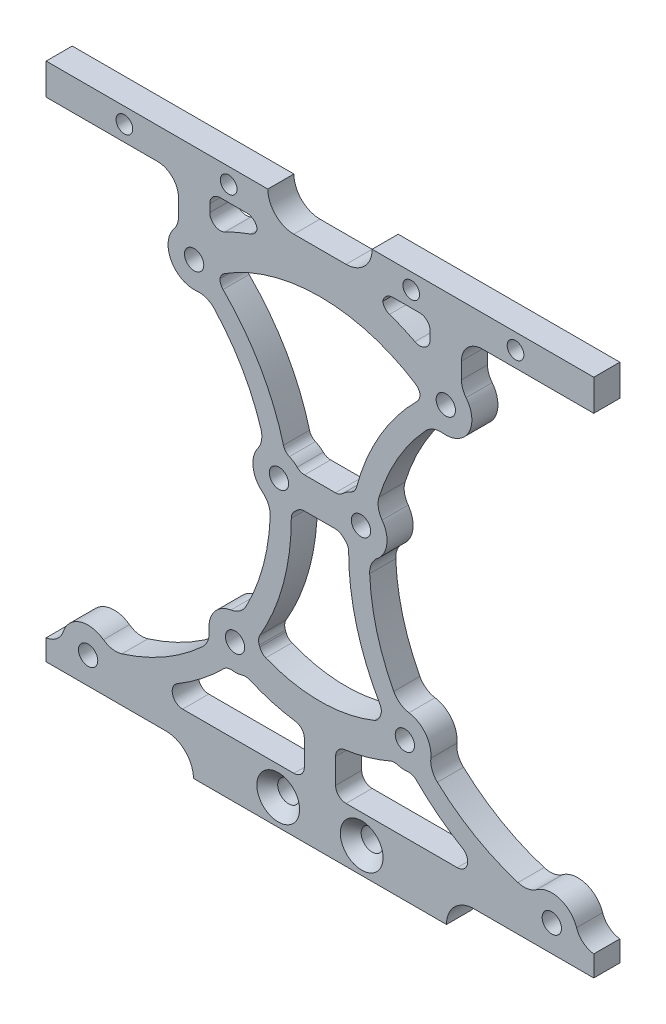
SolidWorks part; units mm, degrees
ref_plane "前视基准面" through (0, 0, 0) normal (0, 0, 1) x (1, 0, 0)
ref_plane "上视基准面" through (0, 0, 0) normal (0, 1, 0) x (1, 0, 0)
ref_plane "右视基准面" through (0, 0, 0) normal (1, 0, 0) x (0, 0, -1)
sketch "草图1" plane through (0, 0, 0) normal (0, 0, 1) x (1, 0, 0)
  line L1 (-50, 0) -> (-50, -42.5) construction
  line L2 (-55, 49.7494) -> (-55, 55)
  line L7 (-55, -49.7494) -> (-55, -55)
  line L8 (55, -55) -> (-55, -55)
  line L9 (-55, 55) -> (55, 55)
  line L10 (0, -55) -> (0, 55) construction
  line L11 (50, 0) -> (50, -42.5) construction
  line L12 (55, -49.7494) -> (55, -55)
  line L13 (55, 49.7494) -> (55, 55)
  arc A1 (-50, -42.5) -> (-44.4526, -42.1364) centre (-50, 0) ccw construction
  circle A2 centre (-44.4526, -42.1364) radius 1.85
  circle A3 centre (-75.8724, -33.7175) radius 1.85
  circle A4 centre (-92.1364, -5.5474) radius 1.85
  circle A5 centre (-83.7175, 25.8724) radius 1.85
  circle A6 centre (-55.5474, 42.1364) radius 1.85
  circle A7 centre (-24.1276, 33.7175) radius 1.85
  circle A8 centre (-7.8636, 5.5474) radius 1.85
  circle A9 centre (-16.2825, -25.8724) radius 1.85
  circle A10 centre (-50, 0) radius 37
  arc A11 (-55, 49.7494) -> (-55, -49.7494) centre (-50, 0) ccw
  arc A12 (50, -42.5) -> (44.4526, -42.1364) centre (50, 0) cw construction
  arc A13 (55, 49.7494) -> (55, -49.7494) centre (50, 0) cw
  circle A14 centre (50, 0) radius 37
  circle A15 centre (16.2825, -25.8724) radius 1.85
  circle A16 centre (7.8636, 5.5474) radius 1.85
  circle A17 centre (24.1276, 33.7175) radius 1.85
  circle A18 centre (55.5474, 42.1364) radius 1.85
  circle A19 centre (83.7175, 25.8724) radius 1.85
  circle A20 centre (92.1364, -5.5474) radius 1.85
  circle A21 centre (75.8724, -33.7175) radius 1.85
  circle A22 centre (44.4526, -42.1364) radius 1.85
  circle A25 centre (8, -47.5) radius 2.1
  circle A27 centre (-8, -47.5) radius 2.1
  point P23 (-50, 0)
  point P26 (50, 0)
  point P50 (0, 55)
  point P51 (0, -55)
  dimension "D1" = 8
extrude "凸台-拉伸1" add sketch "草图1" along normal blind 5
fillet "圆角1" radius 2.5 8 edges at (-55, -49.7494, 2.5) (-55, -55, 2.5) (55, -55, 2.5) (55, -49.7494, 2.5) (55, 49.7494, 2.5) (55, 55, 2.5) (-55, 55, 2.5) (-55, 49.7494, 2.5)
sketch "草图2" plane through (0, 0, 5) normal (0, 0, 1) x (1, 0, 0)
  line L0 (-52.5, 55) -> (-52.5, 52.5)
  line L1 (-52.5, 52.5) -> (52.5, 52.5)
  line L2 (55, 0) -> (-55, 0) construction
  line L3 (-52.5, -52.5) -> (52.5, -52.5)
  line L4 (-52.5, -55) -> (-52.5, -52.5)
  line L5 (0, -55) -> (0, 55) construction
  line L6 (52.5, -55) -> (52.5, -52.5)
  line L7 (52.5, 55) -> (52.5, 52.5)
  line L8 (-52.5, 55) -> (52.5, 55)
  line L9 (52.5, -55) -> (-52.5, -55)
  point P13 (0, -52.5)
  point P14 (0, 52.5)
extrude "切除-拉伸1" cut sketch "草图2" against normal blind 10
sketch "草图3" plane through (0, 0, 5) normal (0, 0, 1) x (1, 0, 0)
  line L0 (-52.5, 52.5) -> (-52.5, -52.5)
  line L1 (-52.5, -52.5) -> (52.5, -52.5)
  line L2 (52.5, -52.5) -> (52.5, 52.5)
  line L3 (52.5, 52.5) -> (-52.5, 52.5)
extrude "切除-拉伸2" cut sketch "草图3" against normal blind 10 flip side to cut
sketch "草图5" plane through (0, 0, 5) normal (0, 0, 1) x (1, 0, 0)
  circle A1 centre (-37.5, 49.5) radius 1.6
  circle A2 centre (-17.5, 49.5) radius 1.6
  circle A3 centre (17.5, 49.5) radius 1.6
  circle A4 centre (37.5, 49.5) radius 1.6
extrude "切除-拉伸3" cut sketch "草图5" against normal blind 10
sketch "草图6" plane through (0, 0, 5) normal (0, 0, 1) x (1, 0, 0)
  line L2 (-52.5, 52.5) -> (-52.5, 36.9154) construction
  line L4 (-3.8636, 2.5474) -> (3.8636, 2.5474)
  line L5 (-3.8636, 8.5474) -> (3.8636, 8.5474)
  line L8 (0, -2.75) -> (0, 2.75) construction
  line L9 (-52.5, 46.5) -> (-52.5, 52.5)
  line L13 (-52.5, 52.5) -> (52.5, 52.5) construction
  line L16 (-52.5, 52.5) -> (52.5, 52.5)
  line L19 (-27.1276, 46.5) -> (-52.5, 46.5)
  line L20 (21.1276, 46.5) -> (21.1276, 39.6188)
  line L21 (-27.1276, 37.7175) -> (-27.1276, 46.5)
  line L22 (-21.1276, 46.5) -> (-21.1276, 39.6188)
  line L23 (27.1276, 37.7175) -> (27.1276, 46.5)
  line L24 (52.5, 46.5) -> (27.1276, 46.5)
  line L25 (52.5, 46.5) -> (52.5, 52.5)
  line L26 (-12, 46.5) -> (-21.1276, 46.5)
  line L27 (-12, 46.5) -> (-12, 43.7997)
  line L28 (12, 46.5) -> (12, 43.7997)
  line L29 (12, 46.5) -> (21.1276, 46.5)
  line L31 (-52.5, -43.2631) -> (-52.5, -52.5)
  line L32 (52.5, -52.5) -> (52.5, -36.9154) construction
  line L33 (49.3363, -43.2089) -> (52.5, -43.2631)
  line L34 (52.5, -43.2631) -> (52.5, -52.5)
  line L35 (52.5, -52.5) -> (-52.5, -52.5)
  line L36 (52.5, -52.5) -> (-52.5, -52.5) construction
  line L37 (-49.3363, -43.2089) -> (-52.5, -43.2631)
  line L39 (3, -42.0254) -> (3, -33.4352)
  line L40 (-3, -42.0254) -> (-3, -33.4352)
  line L47 (-3, -42.0254) -> (-35.3674, -42.0254)
  line L48 (3, -42.0254) -> (35.3674, -42.0254)
  arc A1 (-5.5144, 1.1336) -> (-3.8636, 2.5474) centre (-7.8636, 5.5474) ccw
  arc A3 (-15.3461, -20.9608) -> (-20.7843, -28.048) centre (-16.2825, -25.8724) ccw
  arc A5 (-40.3175, -39.3256) -> (-20.7843, -28.048) centre (-50, 0) ccw
  arc A6 (-35.3674, -42.0254) -> (-17.7424, -30.6545) centre (-50, 0) ccw
  arc A8 (-10.6744, 9.6825) -> (-9.5084, 0.8257) centre (-7.8636, 5.5474) ccw
  arc A9 (-10.6744, 9.6825) -> (-21.952, 29.2157) centre (-50, 0) ccw
  arc A10 (-6.7369, 10.4188) -> (-19.3455, 32.2576) centre (-50, 0) ccw
  arc A11 (-15.3461, -20.9608) -> (-9.5084, 0.8257) centre (-50, 0) ccw
  arc A12 (-12.0412, -23.2245) -> (-5.5144, 1.1336) centre (-50, 0) ccw
  arc A13 (-17.7424, -30.6545) -> (-14.2003, -30.4182) centre (-16.2825, -25.8724) ccw
  arc A14 (-3.8636, 8.5474) -> (-6.7369, 10.4188) centre (-7.8636, 5.5474) ccw
  arc A16 (19.1279, 33.7658) -> (-19.1279, 33.7658) centre (0, 5.5474) ccw
  arc A17 (-12, 43.7997) -> (-21.1276, 39.6188) centre (0, 5.5474) ccw
  arc A20 (3.8636, 8.5474) -> (6.7369, 10.4188) centre (7.8636, 5.5474) cw
  arc A21 (17.7424, -30.6545) -> (14.2003, -30.4182) centre (16.2825, -25.8724) cw
  arc A22 (12.0412, -23.2245) -> (5.5144, 1.1336) centre (50, 0) cw
  arc A23 (15.3461, -20.9608) -> (9.5084, 0.8257) centre (50, 0) cw
  arc A24 (6.7369, 10.4188) -> (19.3455, 32.2576) centre (50, 0) cw
  arc A25 (10.6744, 9.6825) -> (21.952, 29.2157) centre (50, 0) cw
  arc A26 (10.6744, 9.6825) -> (9.5084, 0.8257) centre (7.8636, 5.5474) cw
  arc A28 (35.3674, -42.0254) -> (17.7424, -30.6545) centre (50, 0) cw
  arc A29 (40.3175, -39.3256) -> (20.7843, -28.048) centre (50, 0) cw
  arc A30 (15.3461, -20.9608) -> (20.7843, -28.048) centre (16.2825, -25.8724) cw
  arc A31 (40.3175, -39.3256) -> (49.3363, -43.2089) centre (44.4526, -42.1364) cw
  arc A32 (5.5144, 1.1336) -> (3.8636, 2.5474) centre (7.8636, 5.5474) cw
  arc A34 (-19.3455, 32.2576) -> (-19.1279, 33.7658) centre (-24.1276, 33.7175) ccw
  arc A35 (-27.1276, 37.7175) -> (-21.952, 29.2157) centre (-24.1276, 33.7175) ccw
  arc A36 (27.1276, 37.7175) -> (21.952, 29.2157) centre (24.1276, 33.7175) cw
  arc A37 (19.3455, 32.2576) -> (19.1279, 33.7658) centre (24.1276, 33.7175) cw
  arc A38 (12, 43.7997) -> (21.1276, 39.6188) centre (0, 5.5474) cw
  arc A39 (-40.3175, -39.3256) -> (-49.3363, -43.2089) centre (-44.4526, -42.1364) ccw
  arc A40 (3, -33.4352) -> (14.2003, -30.4182) centre (0, 0) ccw
  arc A42 (-14.2003, -30.4182) -> (-3, -33.4352) centre (0, 0) ccw
  arc A43 (-11.3378, -25.1303) -> (11.3378, -25.1303) centre (0, 0) ccw
  arc A44 (-11.3378, -25.1303) -> (-12.0412, -23.2245) centre (-16.2825, -25.8724) ccw
  arc A48 (11.3378, -25.1303) -> (12.0412, -23.2245) centre (16.2825, -25.8724) cw
  point P15 (0, 0)
  point P23 (-7.8636, 2.5474)
  point P26 (7.8636, 2.5474)
  point P27 (-7.8636, 8.5474)
  point P33 (7.8636, 8.5474)
  point P39 (-24.9781, 40.0639)
  point P41 (0, 2.5474)
  point P46 (-35.8957, 50.5)
  point P50 (-21.1276, 33.7175)
  point P70 (-38.6395, -43.0254)
  point P76 (0, 52.5)
  point P77 (0, 46.5)
  point P78 (0, 8.5474)
  point P80 (-27.1276, 33.7175)
  point P81 (0, -52.5)
  point P97 (0, -43.0254)
  point P100 (14.6876, -26.8099)
  point P103 (0, -43.0254)
  point P105 (-17.8804, -28.4114)
  point P106 (16.129, -29.441)
  point P108 (-14.6846, -23.3333)
  point P109 (13.2462, -24.1789)
  point P113 (0, -31.1409)
  point P115 (3, -43.0254)
  point P116 (3, -31.1409)
  point P117 (-3, -43.0254)
  point P118 (-3, -31.1409)
extrude "切除-拉伸4" cut sketch "草图6" against normal blind 10 flip side to cut
fillet "圆角2" radius 4 18 edges at (27.1276, 46.5, 2.5) (27.1276, 37.7175, 2.5) (21.952, 29.2157, 2.5) (10.6744, 9.6825, 2.5) (9.5084, 0.8257, 2.5) (15.3461, -20.9608, 2.5) (20.7843, -28.048, 2.5) (40.3175, -39.3256, 2.5) (49.3363, -43.2089, 2.5) (-27.1276, 46.5, 2.5) (-27.1276, 37.7175, 2.5) (-21.952, 29.2157, 2.5) (-9.5084, 0.8257, 2.5) (-10.6744, 9.6825, 2.5) (-49.3363, -43.2089, 2.5) (-40.3175, -39.3256, 2.5) (-20.7843, -28.048, 2.5) (-15.3461, -20.9608, 2.5)
fillet "圆角3" radius 2 34 edges at (21.1276, 46.5, 2.5) (12, 46.5, 2.5) (12, 43.7997, 2.5) (21.1276, 39.6188, 2.5) (19.3455, 32.2576, 2.5) (19.1279, 33.7658, 2.5) (6.7369, 10.4188, 2.5) (3.8636, 8.5474, 2.5) (3.8636, 2.5474, 2.5) (5.5144, 1.1336, 2.5) (11.3378, -25.1303, 2.5) (12.0412, -23.2245, 2.5) (17.7424, -30.6545, 2.5) (14.2003, -30.4182, 2.5) (3, -33.4352, 2.5) (3, -42.0254, 2.5) (35.3674, -42.0254, 2.5) (-35.3674, -42.0254, 2.5) (-3, -42.0254, 2.5) (-3, -33.4352, 2.5) (-14.2003, -30.4182, 2.5) (-17.7424, -30.6545, 2.5) (-11.3378, -25.1303, 2.5) (-12.0412, -23.2245, 2.5) (-5.5144, 1.1336, 2.5) (-3.8636, 2.5474, 2.5) (-19.3455, 32.2576, 2.5) (-19.1279, 33.7658, 2.5) (-3.8636, 8.5474, 2.5) (-6.7369, 10.4188, 2.5) (-21.1276, 46.5, 2.5) (-21.1276, 39.6188, 2.5) (-12, 46.5, 2.5) (-12, 43.7997, 2.5)
sketch "草图7" plane through (0, 0, 5) normal (0, 0, 1) x (1, 0, 0)
  line L0 (-52.5, -43.2631) -> (-52.5, -47.2631)
  line L1 (-52.5, -43.2631) -> (-52.5, -52.5) construction
  line L2 (-52.5, -47.2631) -> (-29.5, -47.2631)
  line L4 (-52.5, -47.2631) -> (-52.5, -52.5)
  line L10 (0, -2.75) -> (0, 2.75) construction
  line L11 (-24.2631, -52.5) -> (-52.5, -52.5)
  line L12 (24.2631, -52.5) -> (52.5, -52.5)
  line L13 (52.5, -47.2631) -> (52.5, -52.5)
  line L14 (52.5, -47.2631) -> (29.5, -47.2631)
  line L15 (52.5, -43.2631) -> (52.5, -47.2631)
  arc A2 (-29.5, -47.2631) -> (-24.2631, -52.5) centre (-29.5, -52.5) cw
  arc A3 (29.5, -47.2631) -> (24.2631, -52.5) centre (29.5, -52.5) ccw
extrude "切除-拉伸5" cut sketch "草图7" against normal blind 10 contours L2 L4 | L14 A3 L12 L13 region at (-38.9183, -49.9416, 5)
sketch "草图8" plane through (0, 0, 5) normal (0, 0, 1) x (1, 0, 0)
  line L1 (-52.5, 52.5) -> (52.5, 52.5) construction
  line L2 (5, 47.5) -> (-5, 47.5)
  line L3 (-10, 52.5) -> (10, 52.5)
  arc A0 (5, 47.5) -> (10, 52.5) centre (5, 52.5) ccw
  arc A1 (-5, 47.5) -> (-10, 52.5) centre (-5, 52.5) cw
extrude "切除-拉伸6" cut sketch "草图8" against normal blind 10
chamfer "倒角1" distance 2 angle 45 2 edges at (5.9, -47.5, 5) (-5.9, -47.5, 5)
